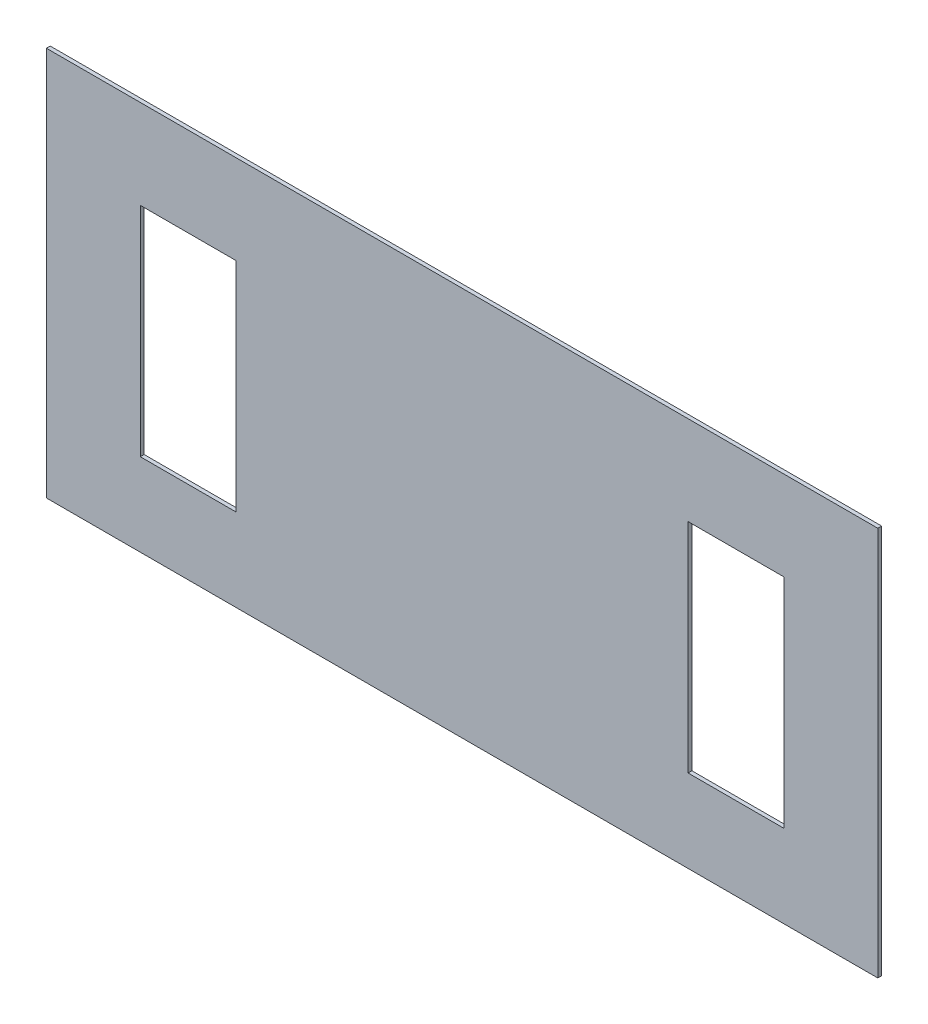
SolidWorks part; units mm, degrees
ref_plane "Front Plane" through (0, 0, 0) normal (0, 0, 1) x (1, 0, 0)
ref_plane "Top Plane" through (0, 0, 0) normal (0, 1, 0) x (1, 0, 0)
ref_plane "Right Plane" through (0, 0, 0) normal (1, 0, 0) x (0, 0, -1)
sketch "Sketch1" plane through (0, 0, 0) normal (0, 0, 1) x (1, 0, 0)
  line L0 (-11.525, -100) -> (-11.525, 103.337)
  line L1 (-11.525, 103.337) -> (422.475, 103.337)
  line L2 (422.475, 103.337) -> (422.475, -100)
  line L3 (422.475, -100) -> (-11.525, -100)
extrude "Boss-Extrude1" add sketch "Sketch1" along normal blind 2
sketch "Sketch2" plane through (0, 0, 2) normal (0, 0, 1) x (1, 0, 0)
  line L0 (205.475, -100) -> (205.475, 103.337) construction
  line L1 (87.4914, -56.8268) -> (37.4914, -56.8268)
  line L2 (87.4914, -56.8268) -> (87.4914, 56.8268)
  line L3 (87.4914, 56.8268) -> (37.4914, 56.8268)
  line L4 (37.4914, -56.8268) -> (37.4914, 56.8268)
  line L5 (87.4914, -56.8268) -> (37.4914, 56.8268) construction
  line L6 (87.4914, 56.8268) -> (37.4914, -56.8268) construction
  line L7 (-11.525, -100) -> (422.475, -100) construction
  line L8 (422.475, 103.337) -> (-11.525, 103.337) construction
  line L9 (323.4586, 56.8268) -> (373.4586, -56.8268) construction
  line L10 (323.4586, -56.8268) -> (373.4586, 56.8268) construction
  line L11 (373.4586, -56.8268) -> (373.4586, 56.8268)
  line L12 (323.4586, 56.8268) -> (373.4586, 56.8268)
  line L13 (323.4586, -56.8268) -> (323.4586, 56.8268)
  line L14 (323.4586, -56.8268) -> (373.4586, -56.8268)
  point P0 (62.4914, 0)
  point P15 (348.4586, 0)
  dimension "D1" = 50
extrude "Cut-Extrude1" cut sketch "Sketch2" against normal through all
